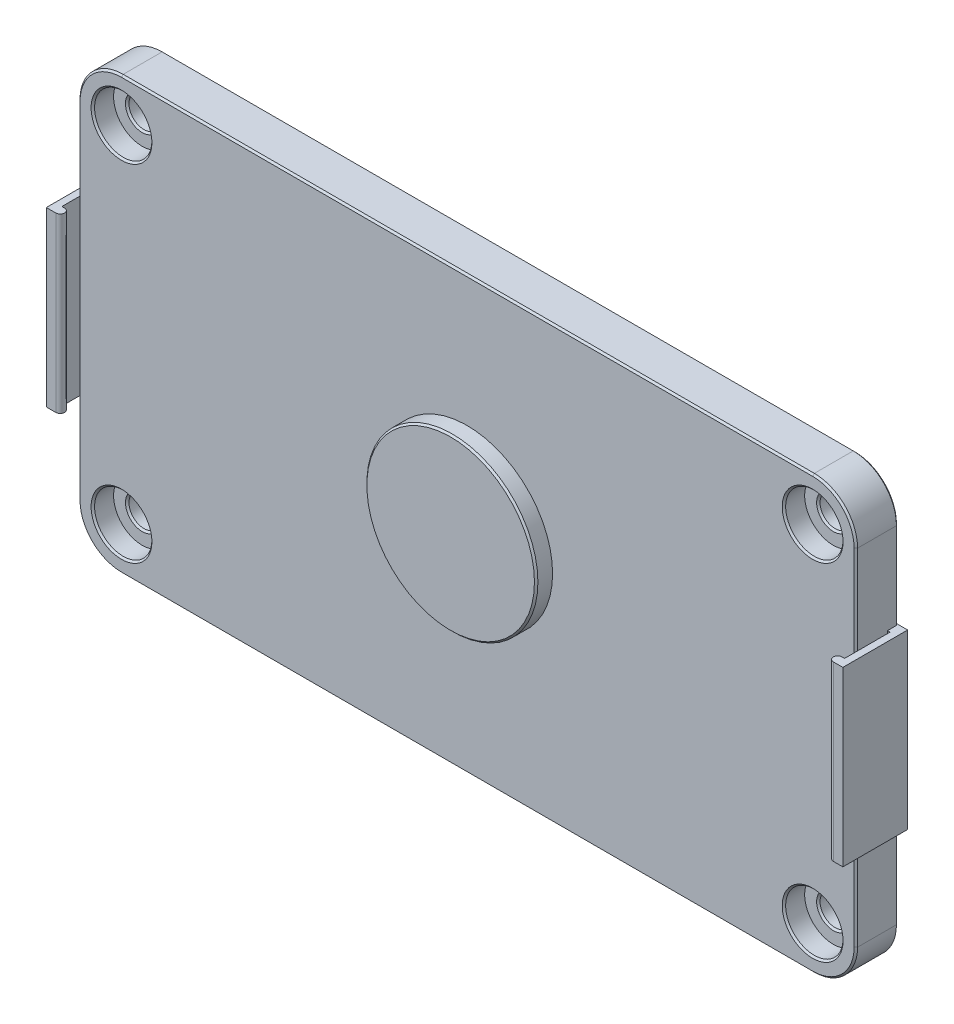
SolidWorks part; units mm, degrees
material "ABS"
ref_plane "Front Plane" through (0, 0, 0) normal (0, 0, 1) x (1, 0, 0)
ref_plane "Top Plane" through (0, 0, 0) normal (0, 1, 0) x (1, 0, 0)
ref_plane "Right Plane" through (0, 0, 0) normal (1, 0, 0) x (0, 0, -1)
sketch "Sketch1" plane through (0, 0, 0) normal (0, 0, 1) x (1, 0, 0)
  line L1 (-50.8, -31.75) -> (50.8, -31.75)
  line L2 (-57.15, -25.4) -> (-57.15, 25.4)
  line L3 (-50.8, 31.75) -> (50.8, 31.75)
  line L4 (57.15, -25.4) -> (57.15, 25.4)
  line L5 (-57.15, -31.75) -> (57.15, 31.75) construction
  line L6 (-57.15, 31.75) -> (57.15, -31.75) construction
  arc A0 (50.8, -31.75) -> (57.15, -25.4) centre (50.8, -25.4) ccw
  arc A1 (50.8, 31.75) -> (57.15, 25.4) centre (50.8, 25.4) cw
  arc A2 (-57.15, 25.4) -> (-50.8, 31.75) centre (-50.8, 25.4) cw
  arc A3 (-50.8, -31.75) -> (-57.15, -25.4) centre (-50.8, -25.4) cw
  circle A4 centre (-50.8, -25.4) radius 2.2098
  circle A5 centre (-50.8, 25.4) radius 2.2098
  circle A6 centre (50.8, 25.4) radius 2.2098
  circle A7 centre (50.8, -25.4) radius 2.2098
  point P0 (0, 0)
  dimension "D3" = 6.35
  dimension "D4" = 4.4196
  dimension "D1" = 114.3
  dimension "D2" = 63.5
extrude "Boss-Extrude1" add sketch "Sketch1" along normal blind 6.223
sketch "Sketch2" plane through (0, 0, 6.223) normal (0, 0, 1) x (1, 0, 0)
  circle A0 centre (-50.8, 25.4) radius 4.2164
  circle A1 centre (50.8, 25.4) radius 4.2164
  circle A2 centre (50.8, -25.4) radius 4.2164
  circle A3 centre (-50.8, -25.4) radius 4.2164
  dimension "D1" = 8.4328
extrude "Cut-Extrude1" cut sketch "Sketch2" against normal blind 3.048
sketch "Sketch4" plane through (0, 0, 0) normal (0, 0, 1) x (1, 0, 0)
  line L0 (-57.15, 25.4) -> (-57.15, -25.4) construction
  line L1 (-57.15, 12.7) -> (-58.547, 12.7)
  line L2 (-57.15, 12.7) -> (-57.15, -12.7)
  line L3 (-57.15, -12.7) -> (-58.547, -12.7)
  line L4 (-58.547, 12.7) -> (-58.547, -12.7)
  line L5 (0, -3.4226) -> (0, 3.4226) construction
  line L6 (57.15, -12.7) -> (58.547, -12.7)
  line L7 (58.547, 12.7) -> (58.547, -12.7)
  line L8 (57.15, 12.7) -> (58.547, 12.7)
  line L9 (57.15, 12.7) -> (57.15, -12.7)
  point P6 (-57.15, 0)
  dimension "D1" = 25.4
  dimension "D2" = 1.397
extrude "Boss-Extrude2" add sketch "Sketch4" along normal blind 1.5557
sketch "Sketch5" plane through (0, -12.7, 0) normal (0, -1, 0) x (1, 0, 0)
  line L0 (-57.531, 1.5557) -> (-58.547, 1.5557)
  line L1 (-57.531, 8.255) -> (-57.15, 8.255)
  line L2 (-58.547, 1.5557) -> (-58.547, 9.525)
  line L3 (-58.547, 9.525) -> (-57.15, 9.525)
  line L6 (-57.531, 8.255) -> (-57.531, 1.5557)
  line L7 (-57.15, 6.223) -> (-57.15, 0) construction
  line L12 (-58.547, 1.5557) -> (-57.15, 1.5557) construction
  line L13 (-58.547, 1.5557) -> (-58.547, 0) construction
  line L19 (-50.8, 6.223) -> (-57.15, 6.223) construction
  line L20 (0, -3.4226) -> (0, 3.4226) construction
  line L21 (58.547, 1.5557) -> (58.547, 9.525)
  line L22 (57.531, 1.5557) -> (58.547, 1.5557)
  line L23 (57.531, 8.255) -> (57.531, 1.5557)
  line L24 (57.531, 8.255) -> (57.15, 8.255)
  line L25 (58.547, 9.525) -> (57.15, 9.525)
  arc A3 (-57.15, 8.255) -> (-57.15, 9.525) centre (-57.15, 8.89) ccw
  arc A4 (57.15, 8.255) -> (57.15, 9.525) centre (57.15, 8.89) cw
  dimension "D2" = 2.667
  dimension "D3" = 0.635
  dimension "D1" = 1.016
extrude "Boss-Extrude3" add sketch "Sketch5" against normal up to surface (25.4 mm away) up to face at (-57.8485, 12.7, 0.7779)
sketch "Sketch6" plane through (0, 0, 6.223) normal (0, 0, 1) x (1, 0, 0)
  circle A0 centre (0, 0) radius 12.573
  dimension "D1" = 25.146
extrude "Boss-Extrude4" add sketch "Sketch6" along normal blind 2.413
chamfer "Chamfer1" distance 0.254 angle 45 27 edges at (12.573, 0, 8.636) (-57.15, -19.05, 0) (57.15, -19.05, 0) (-55.2901, -29.8901, 0) (55.2901, -29.8901, 0) (0, -31.75, 0) (0, 31.75, 6.223) (-55.2901, 29.8901, 6.223) (55.2901, 29.8901, 6.223) (-57.15, 0, 6.223) (57.15, 0, 6.223) (-55.2901, -29.8901, 6.223) (55.2901, -29.8901, 6.223) (0, -31.75, 6.223) (-46.5836, -25.4, 6.223) (-46.5836, 25.4, 6.223) (55.0164, 25.4, 6.223) (55.0164, -25.4, 6.223) (53.0098, 25.4, 3.175) (-48.5902, 25.4, 3.175) (-48.5902, -25.4, 3.175) (53.0098, -25.4, 3.175) (57.15, 19.05, 0) (-57.15, 19.05, 0) (55.2901, 29.8901, 0) (-55.2901, 29.8901, 0) (0, 31.75, 0)
equation "\"wall-thickness\"= .2"
equation "\"tolerance\"= 0.005"
equation "\"D1@Boss-Extrude1\"= .115 + .125 + \"tolerance\""
equation "\"D4@Sketch1\"=.164 + \"tolerance\" * 2"
equation "\"D1@Sketch2\"= .322 + \"tolerance\" * 2"
equation "\"D1@Cut-Extrude1\"= .115 + \"tolerance\""
equation "\"D2@Sketch4\"=.05 + \"tolerance\""
equation "\"D1@Boss-Extrude2\"=\"D1@Boss-Extrude1\" / 4"
equation "\"D1@Sketch6\"=1-\"tolerance\"*2"
equation "\"D1@Boss-Extrude4\"=.1-\"tolerance\""
